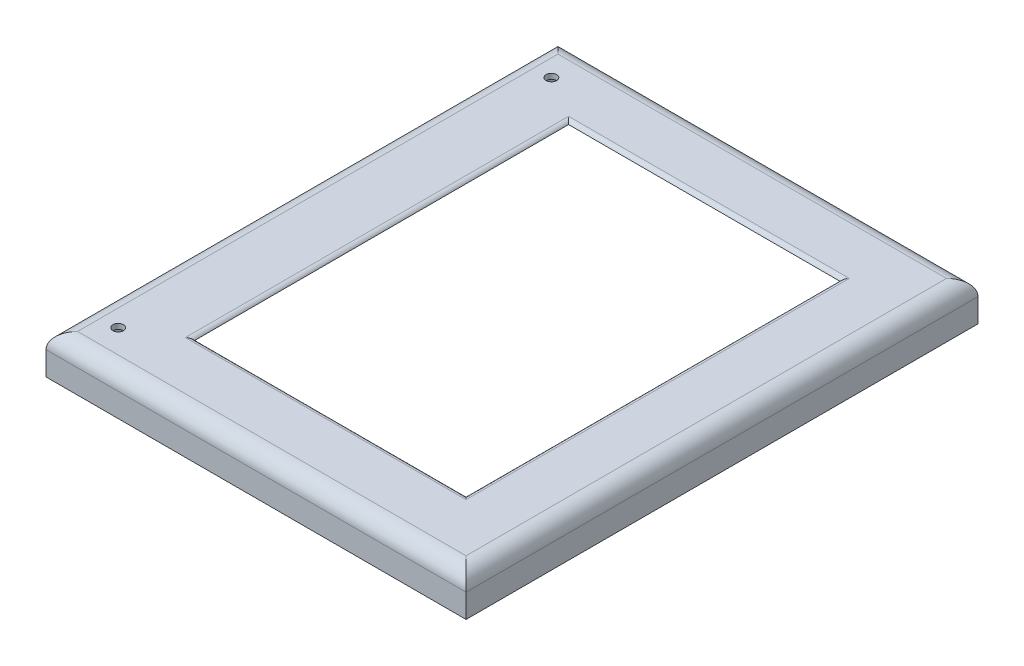
SolidWorks part; units mm, degrees
material "Custom Plastic"
ref_plane "Front" through (0, 0, 0) normal (0, 0, 1) x (1, 0, 0)
ref_plane "Top" through (0, 0, 0) normal (0, 1, 0) x (1, 0, 0)
ref_plane "Right" through (0, 0, 0) normal (1, 0, 0) x (0, 0, -1)
sketch "Sketch1" plane through (0, 0, 0) normal (0, 1, 0) x (1, 0, 0)
  line L1 (-101.6, 123.825) -> (101.6, 123.825)
  line L2 (-101.6, 123.825) -> (-101.6, -123.825)
  line L3 (-101.6, -123.825) -> (101.6, -123.825)
  line L4 (101.6, 123.825) -> (101.6, -123.825)
  line L5 (-101.6, 123.825) -> (101.6, -123.825) construction
  line L6 (-101.6, -123.825) -> (101.6, 123.825) construction
  point P0 (0, 0)
  dimension "D1" = 203.2
  dimension "D2" = 247.65
extrude "Boss-Extrude1" add sketch "Sketch1" along normal blind 19.05
sketch "Sketch2" plane through (0, 19.05, 0) normal (0, 1, 0) x (1, 0, 0)
  line L0 (101.6, -123.825) -> (101.6, 123.825) construction
  line L1 (-62.8, 90.17) -> (67.945, 90.17)
  line L2 (-62.8, 90.17) -> (-62.8, -90.17)
  line L3 (-62.8, -90.17) -> (67.945, -90.17)
  line L4 (67.945, 90.17) -> (67.945, -90.17)
  line L5 (-62.8, 90.17) -> (67.945, -90.17) construction
  line L6 (-62.8, -90.17) -> (67.945, 90.17) construction
  line L7 (101.6, 123.825) -> (-101.6, 123.825) construction
  line L8 (-101.6, -123.825) -> (101.6, -123.825) construction
  line L9 (-101.6, 123.825) -> (-101.6, -123.825) construction
  point P0 (2.5725, 0)
  dimension "D1" = 33.655
  dimension "D2" = 33.655
  dimension "D3" = 33.655
  dimension "D4" = 38.8
fillet "Fillet1" radius 7.62 4 edges at (0, 19.05, 123.825) (-101.6, 19.05, 0) (0, 19.05, -123.825) (101.6, 19.05, 0)
shell "Shell1" thickness 2.54 removed face at (0, 0, 0)
extrude "Cut-Extrude1" cut sketch "Sketch2" against normal up to next
fillet "Fillet2" radius 2.54 4 edges at (-62.8, 19.05, 0) (2.5725, 19.05, 90.17) (67.945, 19.05, 0) (2.5725, 19.05, -90.17)
sketch "Sketch3" plane through (0, 19.05, 0) normal (0, 1, 0) x (1, 0, 0)
  line L0 (-85.725, 104.775) -> (-85.725, -104.775) construction
  line L1 (-101.6, -123.825) -> (-101.6, 123.825) construction
  circle A0 centre (-85.725, 104.775) radius 2.54
  circle A1 centre (-85.725, -104.775) radius 2.54
  point P2 (-85.725, 0)
  dimension "D4" = 5.08
  dimension "D5" = 5.08
  dimension "D1" = 209.55
  dimension "D2" = 15.875
extrude "Cut-Extrude2" cut sketch "Sketch3" against normal up to next
sketch "Sketch4" plane through (0, 16.51, 0) normal (0, -1, 0) x (1, 0, 0)
  line L0 (67.945, -90.17) -> (67.945, 90.17) construction
  line L1 (70.485, -92.71) -> (-65.34, -92.71)
  line L2 (70.485, -92.71) -> (70.485, 92.71)
  line L3 (70.485, 92.71) -> (-65.34, 92.71)
  line L4 (-65.34, -92.71) -> (-65.34, 92.71)
  line L5 (70.485, -92.71) -> (-65.34, 92.71) construction
  line L6 (70.485, 92.71) -> (-65.34, -92.71) construction
  line L7 (-62.8, 90.17) -> (-62.8, -90.17) construction
  line L8 (-62.8, -90.17) -> (67.945, -90.17) construction
  line L9 (67.945, 90.17) -> (-62.8, 90.17) construction
  point P4 (2.5725, 0)
  dimension "D1" = 2.54
  dimension "D2" = 2.54
  dimension "D3" = 2.54
  dimension "D4" = 2.54
extrude "Cut-Extrude3" cut sketch "Sketch4" against normal blind 1.27
equation "\"1.05in-\"=10"
equation "\"D3@Sketch2\"=\"D2@Sketch2\""
equation "\"D1@Sketch2\"=\"D2@Sketch2\""
equation "\"D5@Sketch3\"=\"D4@Sketch3\""
equation "\"D2@Sketch4\"=\"D1@Sketch4\""
equation "\"D3@Sketch4\"=\"D1@Sketch4\""
equation "\"D4@Sketch4\"=\"D1@Sketch4\""
